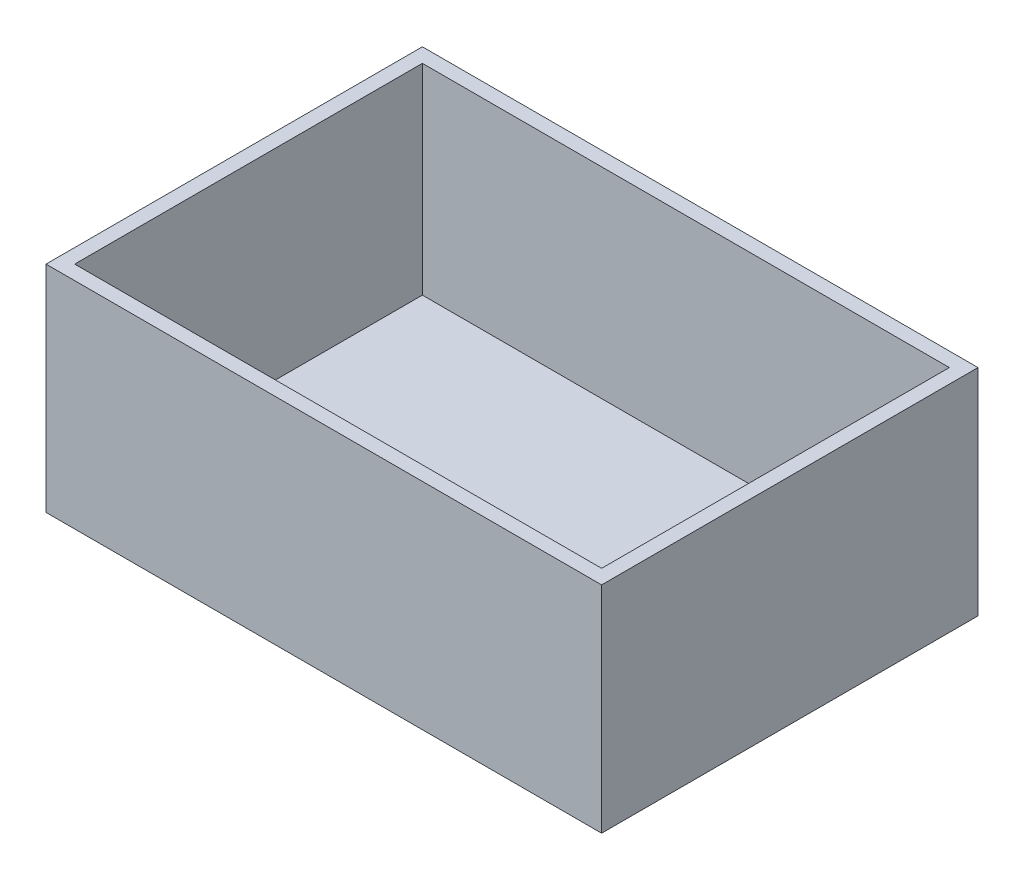
SolidWorks part; units mm, degrees
ref_plane "Alzado" through (0, 0, 0) normal (0, 0, 1) x (1, 0, 0)
ref_plane "Planta" through (0, 0, 0) normal (0, 1, 0) x (1, 0, 0)
ref_plane "Vista lateral" through (0, 0, 0) normal (1, 0, 0) x (0, 0, -1)
sketch "Croquis1" plane through (0, 0, 0) normal (0, 1, 0) x (1, 0, 0)
  line L1 (38.75, -26.25) -> (-38.75, -26.25)
  line L2 (38.75, -26.25) -> (38.75, 26.25)
  line L3 (38.75, 26.25) -> (-38.75, 26.25)
  line L4 (-38.75, -26.25) -> (-38.75, 26.25)
  line L5 (38.75, -26.25) -> (-38.75, 26.25) construction
  line L6 (38.75, 26.25) -> (-38.75, -26.25) construction
  point P0 (0, 0)
  dimension "D1" = 77.5
  dimension "D2" = 52.5
extrude "Saliente-Extruir1" add sketch "Croquis1" along normal blind 30
shell "Vaciado1" thickness 2 removed face at (0, 30, 0)
